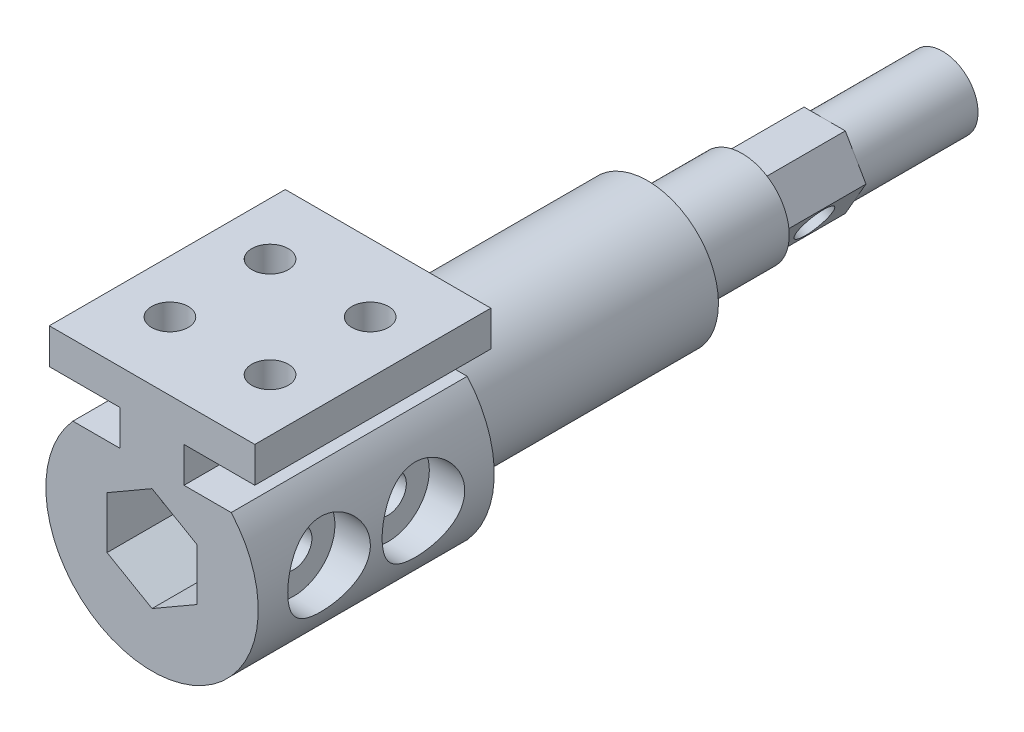
SolidWorks part; units mm, degrees
ref_plane "Front Plane" through (0, 0, 0) normal (0, 0, 1) x (1, 0, 0)
ref_plane "Top Plane" through (0, 0, 0) normal (0, 1, 0) x (1, 0, 0)
ref_plane "Right Plane" through (0, 0, 0) normal (1, 0, 0) x (0, 0, -1)
sketch "Sketch1" plane through (0, 0, 0) normal (0, 0, 1) x (1, 0, 0)
  line L0 (0, 4.4) -> (0, -4.4) construction
  line L1 (-3.8105, -2.2) -> (3.8105, 2.2) construction
  line L2 (-3.8105, 2.2) -> (3.8105, -2.2) construction
  line L21 (0, 0) -> (0, 6) construction
  line L22 (6.7082, 6) -> (-6.7082, 6) construction
  line L27 (-8.7082, 12) -> (8.7082, 12)
  line L32 (-8.7082, 12) -> (-8.7082, 9)
  line L36 (8.7082, 12) -> (8.7082, 9)
  line L40 (-6.7082, 6) -> (-2.7082, 6)
  line L41 (6.7082, 6) -> (2.7082, 6)
  line L42 (2.7082, 6) -> (2.7082, 9)
  line L43 (-2.7082, 6) -> (-2.7082, 9)
  line L44 (-2.7082, 9) -> (-8.7082, 9)
  line L45 (2.7082, 9) -> (8.7082, 9)
  line L46 (0, 4.4) -> (-3.8105, 2.2)
  line L47 (-3.8105, 2.2) -> (-3.8105, -2.2)
  line L48 (-3.8105, -2.2) -> (0, -4.4)
  line L49 (0, -4.4) -> (3.8105, -2.2)
  line L50 (3.8105, -2.2) -> (3.8105, 2.2)
  line L51 (3.8105, 2.2) -> (0, 4.4)
  circle A1 centre (0, 0) radius 4.4 construction
  arc A2 (-6.7082, 6) -> (6.7082, 6) centre (0, 0) ccw
  point P7 (0, 0)
  point P9 (0, 0)
  point P10 (0, 0)
  point P11 (0, 0)
  point P12 (0, 0)
  point P15 (0, 0)
  point P16 (0, 0)
  point P19 (0, 6)
  point P20 (0, 0)
  point P26 (0, 6)
  point P31 (0, 0)
extrude "Boss-Extrude1" add sketch "Sketch1" along normal blind 20
ref_plane "Plane4" through (0, 0, 0) normal (-1, 0, 0) x (0, 0, 1)
sketch "Sketch8" plane through (0, 0, 0) normal (-1, 0, 0) x (0, 0, 1)
  line L0 (0, 0) -> (6, 0) construction
  line L1 (14, 0) -> (6, 0) construction
  circle A0 centre (6, 0) radius 1.55
  circle A1 centre (14, 0) radius 1.55
  point P2 (-6, 0)
  point P3 (15.2321, 0)
  point P4 (-6, 0)
  point P5 (5.2135, 0)
extrude "Cut-Extrude1" cut sketch "Sketch8" against normal blind 9 and the other way blind 9
sketch "Sketch11" plane through (0, 0, 0) normal (0, 0, -1) x (-1, 0, 0)
  circle A0 centre (0, 0) radius 6
extrude "Boss-Extrude12" add sketch "Sketch11" along normal blind 22
sketch "Sketch12" plane through (0, 0, -22) normal (0, 0, -1) x (-1, 0, 0)
  circle A0 centre (0, 0) radius 4
extrude "Boss-Extrude13" add sketch "Sketch12" along normal blind 8
sketch "Sketch13" plane through (0, 0, -30) normal (0, 0, -1) x (-1, 0, 0)
  line L0 (3.5, 0) -> (-3.5, 0) construction
  line L1 (-1.75, -3.0311) -> (1.75, 3.0311) construction
  line L2 (1.75, -3.0311) -> (-1.75, 3.0311) construction
  line L3 (1.75, 3.0311) -> (-1.75, 3.0311)
  line L4 (-1.75, 3.0311) -> (-3.5, 0)
  line L5 (-3.5, 0) -> (-1.75, -3.0311)
  line L6 (-1.75, -3.0311) -> (1.75, -3.0311)
  line L7 (1.75, -3.0311) -> (3.5, 0)
  line L8 (3.5, 0) -> (1.75, 3.0311)
  point P6 (0, 0)
  point P9 (0, 0)
  point P12 (0, 0)
extrude "Boss-Extrude14" add sketch "Sketch13" along normal blind 7 contours L4 L5 L6 L7 L8 L3
sketch "Sketch14" plane through (2.625, -1.5155, 0) normal (0.866, -0.5, 0) x (0, 0, -1)
  line L0 (30, 0) -> (37, 0) construction
  line L1 (30, 1.75) -> (30, -1.75) construction
  line L2 (37, 1.75) -> (37, -1.75) construction
  circle A0 centre (33.5, 0) radius 1.55
extrude "Cut-Extrude2" cut sketch "Sketch14" against normal blind 6.1
sketch "Sketch15" plane through (0, 0, -37) normal (0, 0, -1) x (-1, 0, 0)
  circle A0 centre (0, 0) radius 3
extrude "Boss-Extrude15" add sketch "Sketch15" along normal blind 10
sketch "Sketch16" plane through (0, 0, 0) normal (-1, 0, 0) x (0, 0, 1)
  circle A1 centre (6, 0) radius 3.5
  circle A2 centre (14, 0) radius 3.5
extrude "Cut-Extrude5" cut sketch "Sketch16" against normal blind 3 from offset 9
extrude "Cut-Extrude6" cut sketch "Sketch16<2>" along normal blind 3 from offset 9 offset against normal yes
sketch "Sketch16<2>" plane through (0, 0, 0) normal (-1, 0, 0) x (0, 0, 1) same geometry as "Sketch16"
sketch "Sketch17" plane through (0, 12, 0) normal (0, 1, 0) x (1, 0, 0)
  line L0 (-8.7082, 0) -> (8.7082, -20) construction
  line L1 (8.7082, 0) -> (-8.7082, -20) construction
  line L2 (-4.2426, -14.2426) -> (4.2426, -5.7574) construction
  line L3 (4.2426, -14.2426) -> (-4.2426, -5.7574) construction
  circle A0 centre (0, -10) radius 6 construction
  circle A1 centre (-4.2426, -5.7574) radius 1.55
  circle A2 centre (4.2426, -5.7574) radius 1.55
  circle A3 centre (4.2426, -14.2426) radius 1.55
  circle A4 centre (-4.2426, -14.2426) radius 1.55
  point P13 (0, -10)
  point P16 (0, -10)
  point P26 (0, -10)
  dimension "D1" = 4
extrude "Cut-Extrude7" cut sketch "Sketch17" against normal up to surface (3 mm away) up to face at (-5.7082, 9, 10)
